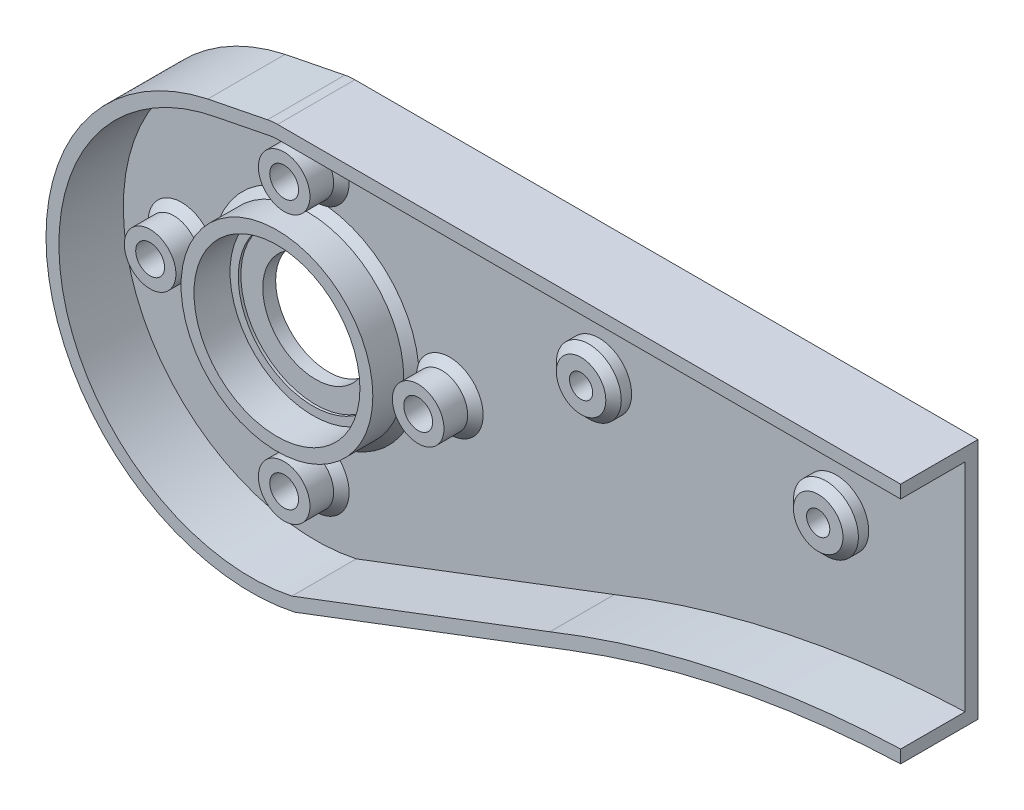
SolidWorks part; units mm, degrees
note: The reader was unsure of these and kept them because the rebuilt part matched: shared geometry of "Schizzo1<3>", "Schizzo3<3>", "Schizzo3<4>", "Schizzo3<5>".
material "ABS"
ref_plane "Piano frontale" through (0, 0, 0) normal (0, 0, 1) x (1, 0, 0)
ref_plane "Piano superiore" through (0, 0, 0) normal (0, 1, 0) x (1, 0, 0)
ref_plane "Piano destro" through (0, 0, 0) normal (1, 0, 0) x (0, 0, -1)
sketch "Schizzo1" plane through (0, 0, 0) normal (0, 0, 1) x (1, 0, 0)
  line L0 (5.1235, 41.4) -> (126, 41.4)
  line L1 (-8.4161, 38.9) -> (3.1704, 41.2074)
  line L2 (46, 26.4263) -> (46, 7.4358) construction
  line L3 (46, 7.4358) -> (126, 7.4358) construction
  line L4 (55, 17.9) -> (101, 17.9) construction
  line L5 (126, 41.4) -> (126, -5.6)
  line L6 (126, -5.6) -> (96, -5.6) construction
  line L7 (8.4161, -38.9) -> (96, -5.6) construction
  line L8 (8.4161, -38.9) -> (-8.4161, 38.9) construction
  line L10 (126, 38.9) -> (5.37, 38.9)
  line L11 (3.4169, 38.7074) -> (-6.661, 36.7004)
  line L12 (7.8874, -36.4565) -> (57.9534, -17.4211)
  line L13 (95.62, -3.1) -> (126, -3.1) construction
  line L14 (61.9889, -18.5312) -> (61.1104, -16.2208) construction
  line L15 (61.9889, -18.5312) -> (133.0662, -205.4751) construction
  line L16 (61.1104, -16.2208) -> (95.62, -3.1) construction
  line L17 (61.9889, -18.5312) -> (8.4161, -38.9)
  arc A0 (-8.4161, 38.9) -> (8.4161, -38.9) centre (0, 0) ccw
  circle A1 centre (55, 17.9) radius 8.0303 construction
  circle A2 centre (101, 17.9) radius 6.341 construction
  arc A3 (-6.661, 36.7004) -> (7.8874, -36.4565) centre (0, 0) ccw
  arc A4 (126, -5.6) -> (61.9889, -18.5312) centre (133.0662, -205.4751) ccw
  arc A5 (126, -3.0985) -> (57.9534, -17.4211) centre (133.0662, -205.4751) ccw
  arc A6 (5.37, 38.9) -> (3.4169, 38.7074) centre (5.37, 28.9) ccw
  arc A7 (5.1235, 41.4) -> (3.1704, 41.2074) centre (5.1235, 31.4) ccw
  point P31 (4.1374, 41.4)
  dimension "D1" = 79.6
  dimension "D4" = 23.5
  dimension "D10" = 25
  dimension "D12" = 2.5
  dimension "D15" = 400
  dimension "D18" = 2.5
  dimension "D19" = 10
  dimension "D2" = 55
  dimension "D3" = 17.9
  dimension "D5" = 12.8
  dimension "D6" = 2.5
  dimension "D7" = 9
  dimension "D8" = 80
  dimension "D9" = 25
  dimension "D11" = 30
  dimension "D13" = 47
  dimension "D14" = 2.5
  dimension "D16" = 2.5
  dimension "D17" = 2.5
extrude "Estrusione-Estrusione1" add sketch "Schizzo1" along normal blind 2.5
extrude "Estrusione-Estrusione2" add sketch "Schizzo1<3>" along normal blind 15 contours A3 L11 L10 L5 L0 L1 A0 L7 L6 L13 L12
sketch "Schizzo1<3>" plane through (0, 0, 0) normal (0, 0, 1) x (1, 0, 0) same geometry as "Schizzo1"
sketch "Schizzo2" plane through (0, 0, 0) normal (0, 0, -1) x (-1, 0, 0)
  line L0 (-26, 0) -> (26, 0) construction
  line L1 (0, -26) -> (0, 26) construction
  circle A0 centre (0, 0) radius 10.25
  circle A1 centre (0, 0) radius 26 construction
  circle A2 centre (0, -26) radius 2.8
  circle A3 centre (26, 0) radius 2.8
  circle A4 centre (0, 26) radius 2.8
  circle A5 centre (-26, 0) radius 2.8 construction
  dimension "D1" = 5.6
  dimension "D2" = 52
  dimension "D3" = 20.5
extrude "Taglio-Estrusione1" cut sketch "Schizzo2" against normal blind 15
sketch "Schizzo3" plane through (0, 0, 2.5) normal (0, 0, 1) x (1, 0, 0)
  line L0 (126, 38.9) -> (126, -3.0985) construction
  line L1 (55, 17.9) -> (101, 17.9) construction
  line L2 (26, 0) -> (0, 0) construction
  circle A0 centre (0, 0) radius 14.5
  circle A1 centre (0, 0) radius 16.1
  circle A2 centre (0, 0) radius 18.6
  circle A3 centre (0, 26) radius 2.8
  circle A4 centre (0, 26) radius 5
  circle A5 centre (26, 0) radius 2.8
  circle A6 centre (26, 0) radius 5
  circle A7 centre (0, -26) radius 2.8
  circle A8 centre (0, -26) radius 5
  circle A9 centre (-26, 0) radius 2.8
  circle A10 centre (-26, 0) radius 5
  circle A11 centre (55, 17.9) radius 6.3
  circle A12 centre (101, 17.9) radius 6.3
  circle A13 centre (55, 17.9) radius 2.25
  circle A14 centre (101, 17.9) radius 2.25
  dimension "D1" = 29
  dimension "D2" = 32.2
  dimension "D3" = 37.2
  dimension "D4" = 10
  dimension "D5" = 5.6
  dimension "D6" = 12.6
  dimension "D10" = 4.5
  dimension "D7" = 25
  dimension "D8" = 55
  dimension "D9" = 17.9
  dimension "D11" = 26
extrude "Estrusione-Estrusione3" add sketch "Schizzo3" along normal blind 0.5 contours A1 A0
extrude "Estrusione-Estrusione4" add sketch "Schizzo3<3>" along normal blind 7.5 contours A2 A1
sketch "Schizzo3<3>" plane through (0, 0, 2.5) normal (0, 0, 1) x (1, 0, 0) same geometry as "Schizzo3"
extrude "Estrusione-Estrusione5" add sketch "Schizzo3<4>" along normal blind 6.1
sketch "Schizzo3<4>" plane through (0, 0, 2.5) normal (0, 0, 1) x (1, 0, 0) same geometry as "Schizzo3"
extrude "Estrusione-Estrusione6" add sketch "Schizzo3<5>" along normal blind 3.5
sketch "Schizzo3<5>" plane through (0, 0, 2.5) normal (0, 0, 1) x (1, 0, 0) same geometry as "Schizzo3"
chamfer "Smusso1" distance 1.5 angle 45 7 edges at (18.6, 0, 2.5) (5, -26, 2.5) (31, 0, 2.5) (5, 26, 2.5) (-21, 0, 2.5) (107.3, 17.9, 6) (61.3, 17.9, 6)
hole_wizard "Foro per Vite M4-1" positions "Schizzo3D1" profile "Schizzo5" hole size "M4" standard "ISO"
sketch3d "Schizzo3D1"
  line L0 (101, 17.9, 0) -> (55, 17.9, 0) construction
  line L2 (126, 41.4, 0) -> (126, -5.6, 0) construction
  line L3 (0, 0, 0) -> (0, 47.825, 0) construction
  point P1 (55, 17.9, 0)
  point P3 (101, 17.9, 0)
  dimension "D1" = 25
  dimension "D2" = 55
  dimension "D3" = 17.9
sketch "Schizzo5" plane through (55, 17.9, 0) normal (1, 0, 0) x (0, 1, 0)
  line L0 (0, 0) -> (0, 51.3519)
  line L1 (0, 51.3519) -> (2.25, 50)
  line L2 (2.25, 50) -> (2.25, 0)
  line L5 (2.25, 0) -> (0, 0)
  line L10 (0, 51.3519) -> (-2.25, 50) construction
  line L11 (0, -6.35) -> (0, 107.95) construction
  dimension "Hole Dia." = 4.5
  dimension "Hole Depth" = 50
  dimension "Drill Angle" = 118
